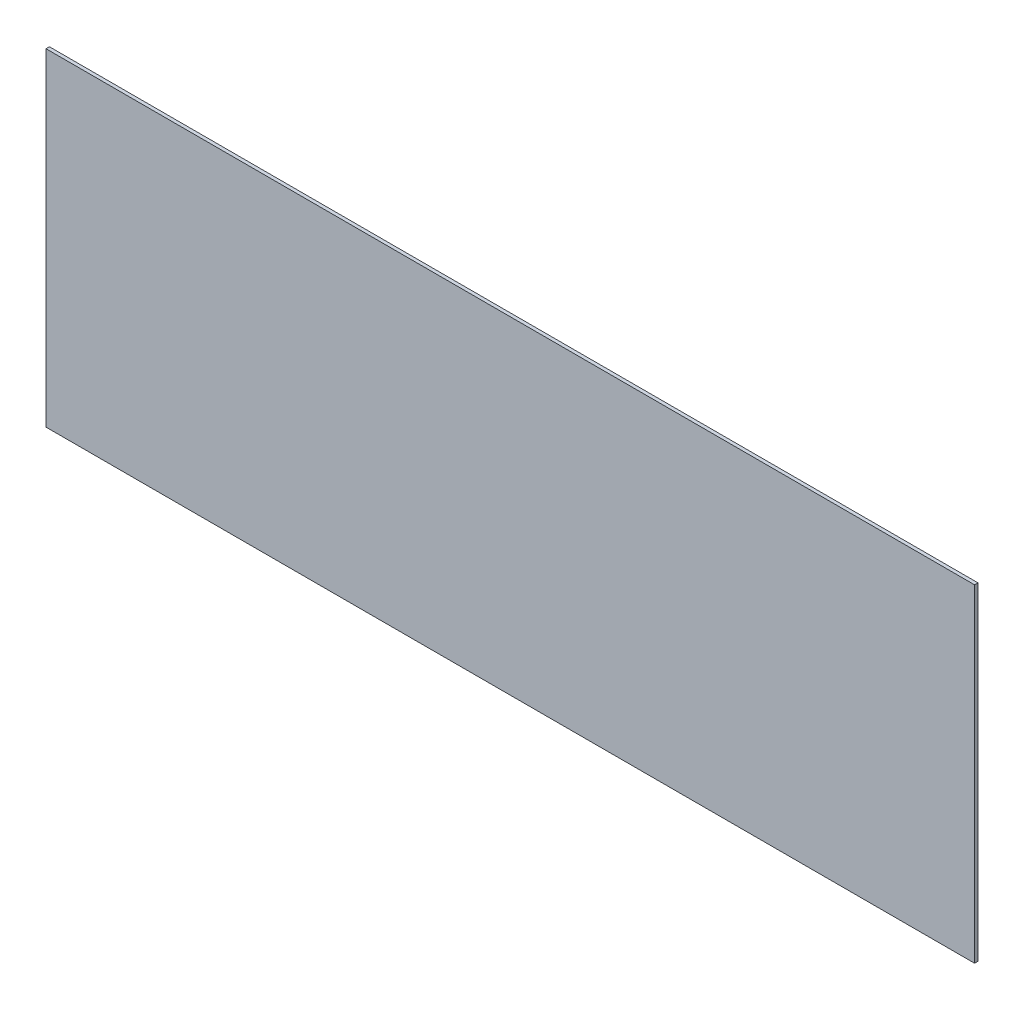
SolidWorks part; units mm, degrees
ref_plane "Front Plane" through (0, 0, 0) normal (0, 0, 1) x (1, 0, 0)
ref_plane "Top Plane" through (0, 0, 0) normal (0, 1, 0) x (1, 0, 0)
ref_plane "Right Plane" through (0, 0, 0) normal (1, 0, 0) x (0, 0, -1)
sketch "Sketch1" plane through (0, 0, 0) normal (0, 0, 1) x (1, 0, 0)
  line L0 (-238.8538, 118.6227) -> (624.7462, 118.6227) construction
  line L1 (-238.8538, 271.0227) -> (624.7462, 271.0227)
  line L2 (-238.8538, 271.0227) -> (-238.8538, -33.7773)
  line L3 (-238.8538, -33.7773) -> (624.7462, -33.7773)
  line L4 (624.7462, 271.0227) -> (624.7462, -33.7773)
  line L5 (192.9462, 271.0227) -> (192.9462, -33.7773) construction
  dimension "D1" = 863.6
  dimension "D2" = 304.8
extrude "Boss-Extrude1" add sketch "Sketch1" along normal blind 3.175
